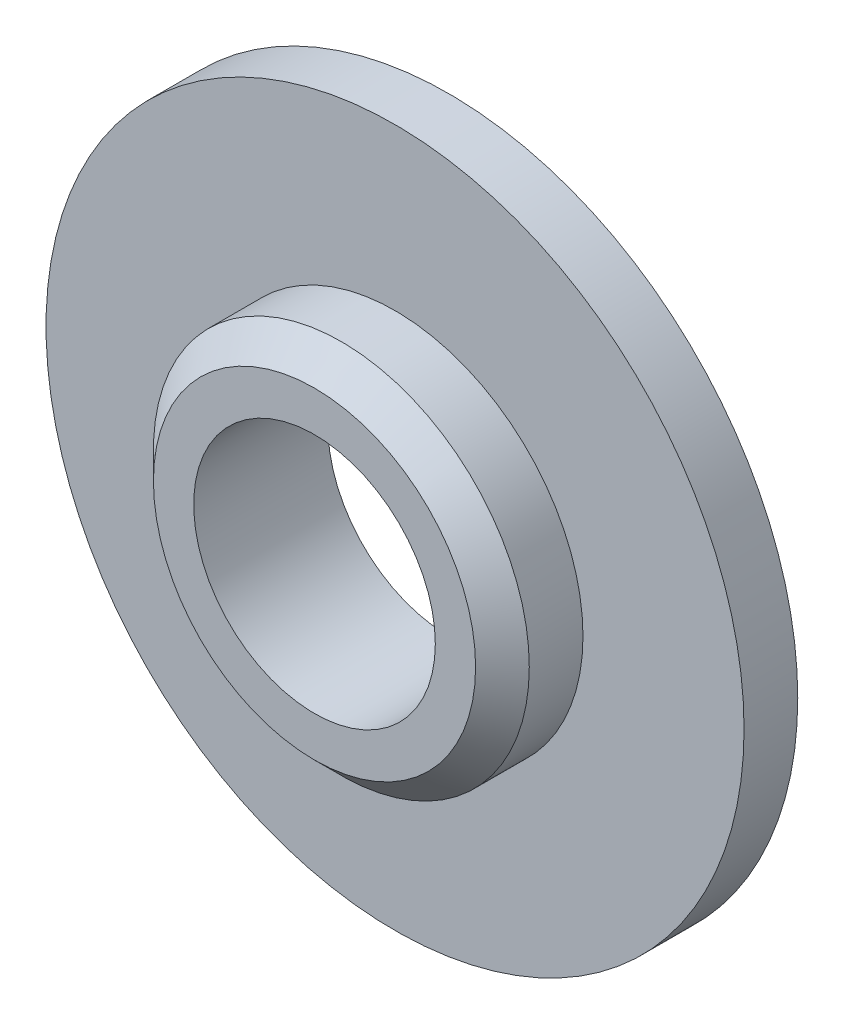
SolidWorks part; units mm, degrees
note: The reader was unsure of these and kept them because the rebuilt part matched: shared geometry of "Sketch1<3>".
material "PA Type 6"
ref_plane "Front Plane" through (0, 0, 0) normal (0, 0, 1) x (1, 0, 0)
ref_plane "Top Plane" through (0, 0, 0) normal (0, 1, 0) x (1, 0, 0)
ref_plane "Right Plane" through (0, 0, 0) normal (1, 0, 0) x (0, 0, -1)
sketch "Sketch1" plane through (0, 0, 0) normal (0, 0, 1) x (1, 0, 0)
  circle A0 centre (0, 0) radius 13
  circle A1 centre (0, 0) radius 4.5
  circle A2 centre (0, 0) radius 7
  dimension "D1" = 26
  dimension "D2" = 9
  dimension "D3" = 14
extrude "Boss-Extrude1" add sketch "Sketch1" along normal blind 2 contours A0 A2 | A2 A1 | A1
extrude "Boss-Extrude2" add sketch "Sketch1<3>" along normal blind 5 contours A2 A1
sketch "Sketch1<3>" plane through (0, 0, 0) normal (0, 0, 1) x (1, 0, 0) same geometry as "Sketch1"
chamfer "Chamfer1" distance 1 angle 45 1 edges at (7, 0, 5)
